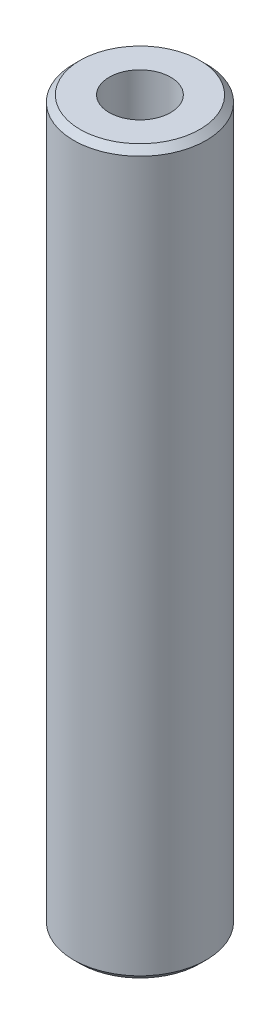
SolidWorks part; units mm, degrees
ref_plane "Front Plane" through (0, 0, 0) normal (0, 0, 1) x (1, 0, 0)
ref_plane "Top Plane" through (0, 0, 0) normal (0, 1, 0) x (1, 0, 0)
ref_plane "Right Plane" through (0, 0, 0) normal (1, 0, 0) x (0, 0, -1)
sketch "Sketch1" plane through (0, 0, 0) normal (0, 1, 0) x (1, 0, 0)
  circle A0 centre (0, 0) radius 55
  dimension "SHAFT_OD" = 110
extrude "Boss-Extrude1" add sketch "Sketch1" along normal blind 600
sketch "Sketch2" plane through (0, 0, 0) normal (0, 1, 0) x (1, 0, 0)
  circle A0 centre (0, 0) radius 25.4993
  dimension "BORE_D" = 50.9986
extrude "Cut-Extrude1" cut sketch "Sketch2" along normal through all
chamfer "Chamfer1" distance 5.2843 angle 45 2 edges at (0, 600, 55) (0, 0, 55)
